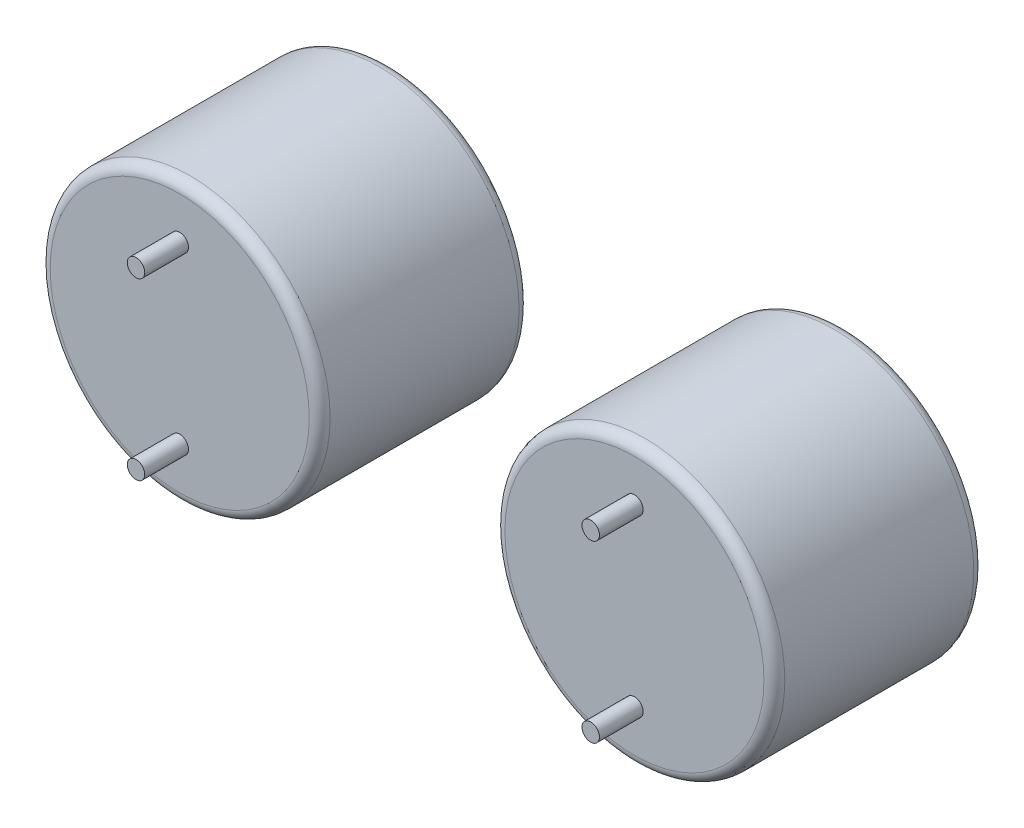
SolidWorks part; units mm, degrees
ref_plane "Front Plane" through (0, 0, 0) normal (0, 0, 1) x (1, 0, 0)
ref_plane "Top Plane" through (0, 0, 0) normal (0, 1, 0) x (1, 0, 0)
ref_plane "Right Plane" through (0, 0, 0) normal (1, 0, 0) x (0, 0, -1)
sketch "Sketch5" plane through (0, 0, 0) normal (0, 1, 0) x (1, 0, 0)
  line L0 (14.0786, 6) -> (13, 6)
  line L1 (13, 6) -> (13, 0)
  line L2 (13, 0) -> (20.4054, 0)
  line L3 (21, 0.6) -> (21, 11.4054)
  line L4 (20.4, 12) -> (19.5, 12)
  line L5 (19.5, 12) -> (19.5, 11.6)
  line L6 (19.5, 11.6) -> (20.2, 11.6)
  line L7 (20.2, 11.6) -> (20.2, 1)
  line L8 (20.2, 1) -> (19.3924, 1)
  line L9 (19.3924, 1) -> (19.3924, 5.425)
  line L10 (19.3924, 5.425) -> (14.3166, 5.425)
  line L11 (14.3166, 5.425) -> (18.2424, 8.0026)
  line L12 (18.2424, 8.0026) -> (18.2424, 8.4784)
  line L13 (18.2424, 8.4784) -> (14.0786, 6)
  line L14 (13, 12.0012) -> (13, -0.0012) construction
  line L16 (-13, 6) -> (-13, 0)
  line L29 (-13, 11.1961) -> (-13, -0.8064) construction
  line L30 (-18.2424, 8.4784) -> (-14.0786, 6)
  line L31 (-18.2424, 8.0026) -> (-18.2424, 8.4784)
  line L32 (-14.3166, 5.425) -> (-18.2424, 8.0026)
  line L33 (-19.3924, 5.425) -> (-14.3166, 5.425)
  line L34 (-19.3924, 1) -> (-19.3924, 5.425)
  line L35 (-20.2, 1) -> (-19.3924, 1)
  line L36 (-20.2, 11.6) -> (-20.2, 1)
  line L37 (-19.5, 11.6) -> (-20.2, 11.6)
  line L38 (-19.5, 12) -> (-19.5, 11.6)
  line L39 (-20.4, 12) -> (-19.5, 12)
  line L40 (-21, 0.6) -> (-21, 11.4054)
  line L41 (-13, 0) -> (-20.4054, 0)
  line L42 (-14.0786, 6) -> (-13, 6)
  arc A0 (20.4054, 0) -> (21, 0.6) centre (20.4, 0.6) ccw
  arc A1 (21, 11.4054) -> (20.4, 12) centre (20.4, 11.4) ccw
  arc A4 (-21, 11.4054) -> (-20.4, 12) centre (-20.4, 11.4) cw
  arc A5 (-20.4054, 0) -> (-21, 0.6) centre (-20.4, 0.6) cw
  dimension "D4" = 0.6
  dimension "D10" = 6
  dimension "D1" = 12
  dimension "D2" = 16
  dimension "D3" = 21
  dimension "D5" = 13
  dimension "D6" = 0.8
  dimension "D7" = 1
  dimension "D8" = 6
  dimension "D9" = 16
  dimension "D11" = 21
  dimension "D12" = 0.8
  dimension "D13" = 13
  dimension "D14" = 0.6
  dimension "D15" = 0.6
  dimension "D16" = 0.4
revolve "T" add sketch "Sketch5" angle 360 about L14 region at (17.0946, 0, -3.6231) reverse direction yes
revolve "R" add sketch "Sketch5<3>" angle 360 about L29 region at (-17.0946, 0, -3.6231)
sketch "Sketch5<3>" plane through (0, 0, 0) normal (0, 1, 0) x (1, 0, 0) same geometry as "Sketch5"
sketch "Sketch11" plane through (0, 0, 0) normal (0, 0, 1) x (1, 0, 0)
  circle A0 centre (-13, 5) radius 0.5
  circle A1 centre (-13, -5) radius 0.5
  circle A2 centre (13, 5) radius 0.5
  circle A3 centre (13, -5) radius 0.5
  circle A4 centre (13, 0) radius 7.4054 construction
  circle A5 centre (-13, 0) radius 7.4054 construction
  circle A6 centre (13, 0) radius 7.4054 construction
  circle A7 centre (-13, 0) radius 7.4054 construction
  dimension "D3" = 1
  dimension "D1" = 5
  dimension "D2" = 5
extrude "Pins" add sketch "Sketch11" along normal blind 2.5
